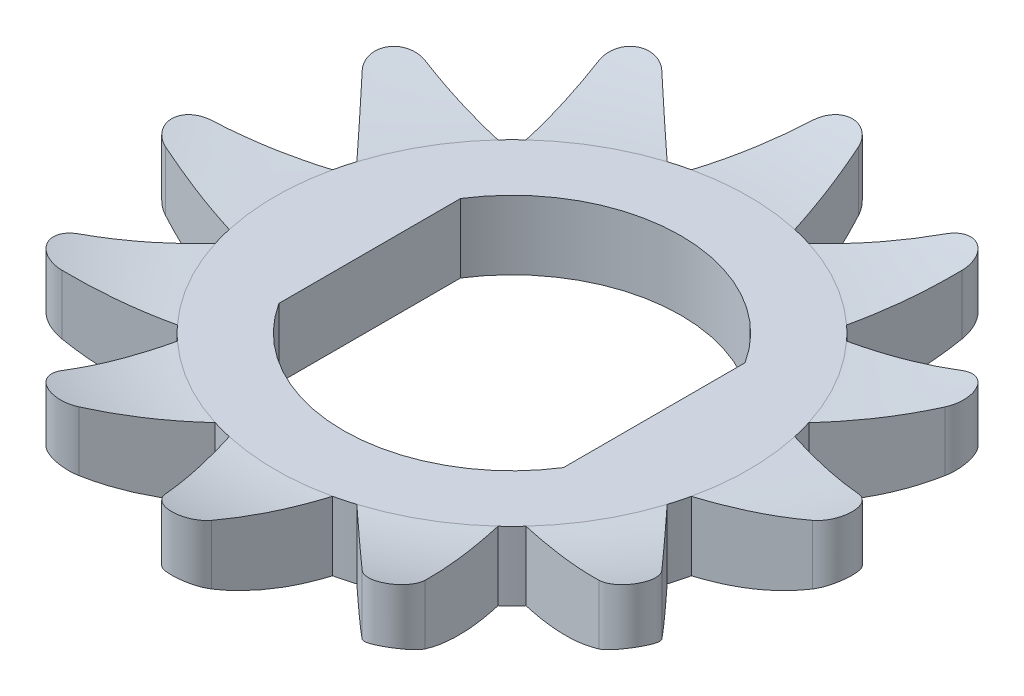
SolidWorks part; units mm, degrees
material "1060 Alloy"
ref_plane "Front Plane" through (0, 0, 0) normal (0, 0, 1) x (1, 0, 0)
ref_plane "Top Plane" through (0, 0, 0) normal (0, 1, 0) x (1, 0, 0)
ref_plane "Right Plane" through (0, 0, 0) normal (1, 0, 0) x (0, 0, -1)
sketch "Sketch1" plane through (0, 0, 0) normal (0, 1, 0) x (1, 0, 0)
  line L0 (0, 6.875) -> (0, 9.88) construction
  line L1 (-1.5, 6.7094) -> (-0.6685, 9.3876)
  line L2 (0.6685, 9.3876) -> (1.5, 6.7094)
  line L3 (2.0556, 6.5605) -> (4.1148, 8.4641)
  line L4 (5.2727, 7.7956) -> (4.6537, 5.0605)
  line L5 (5.0605, 4.6537) -> (7.7956, 5.2727)
  line L6 (8.4641, 4.1148) -> (6.5605, 2.0556)
  line L7 (6.7094, 1.5) -> (9.3876, 0.6685)
  line L8 (9.3876, -0.6685) -> (6.7094, -1.5)
  line L9 (6.5605, -2.0556) -> (8.4641, -4.1148)
  line L10 (7.7956, -5.2727) -> (5.0605, -4.6537)
  line L11 (4.6537, -5.0605) -> (5.2727, -7.7956)
  line L12 (4.1148, -8.4641) -> (2.0556, -6.5605)
  line L13 (1.5, -6.7094) -> (0.6685, -9.3876)
  line L14 (-0.6685, -9.3876) -> (-1.5, -6.7094)
  line L15 (-2.0556, -6.5605) -> (-4.1148, -8.4641)
  line L16 (-5.2727, -7.7956) -> (-4.6537, -5.0605)
  line L17 (-5.0605, -4.6537) -> (-7.7956, -5.2727)
  line L18 (-8.4641, -4.1148) -> (-6.5605, -2.0556)
  line L19 (-6.7094, -1.5) -> (-9.3876, -0.6685)
  line L20 (-9.3876, 0.6685) -> (-6.7094, 1.5)
  line L21 (-6.5605, 2.0556) -> (-8.4641, 4.1148)
  line L22 (-7.7956, 5.2727) -> (-5.0605, 4.6537)
  line L23 (-4.6537, 5.0605) -> (-5.2727, 7.7956)
  line L24 (-4.1148, 8.4641) -> (-2.0556, 6.5605)
  arc A1 (-4.6537, 5.0605) -> (-5.0605, 4.6537) centre (0, 0) ccw
  arc A2 (-0.6685, 9.3876) -> (0.6685, 9.3876) centre (0, 9.18) cw
  arc A3 (4.1148, 8.4641) -> (5.2727, 7.7956) centre (4.59, 7.9501) cw
  arc A4 (7.7956, 5.2727) -> (8.4641, 4.1148) centre (7.9501, 4.59) cw
  arc A5 (9.3876, 0.6685) -> (9.3876, -0.6685) centre (9.18, 0) cw
  arc A6 (8.4641, -4.1148) -> (7.7956, -5.2727) centre (7.9501, -4.59) cw
  arc A7 (5.2727, -7.7956) -> (4.1148, -8.4641) centre (4.59, -7.9501) cw
  arc A8 (0.6685, -9.3876) -> (-0.6685, -9.3876) centre (0, -9.18) cw
  arc A9 (-4.1148, -8.4641) -> (-5.2727, -7.7956) centre (-4.59, -7.9501) cw
  arc A10 (-7.7956, -5.2727) -> (-8.4641, -4.1148) centre (-7.9501, -4.59) cw
  arc A11 (-9.3876, -0.6685) -> (-9.3876, 0.6685) centre (-9.18, 0) cw
  arc A12 (-8.4641, 4.1148) -> (-7.7956, 5.2727) centre (-7.9501, 4.59) cw
  arc A13 (-5.2727, 7.7956) -> (-4.1148, 8.4641) centre (-4.59, 7.9501) cw
  arc A14 (-6.5605, 2.0556) -> (-6.7094, 1.5) centre (0, 0) ccw
  arc A15 (-6.7094, -1.5) -> (-6.5605, -2.0556) centre (0, 0) ccw
  arc A16 (-5.0605, -4.6537) -> (-4.6537, -5.0605) centre (0, 0) ccw
  arc A17 (-2.0556, -6.5605) -> (-1.5, -6.7094) centre (0, 0) ccw
  arc A18 (1.5, -6.7094) -> (2.0556, -6.5605) centre (0, 0) ccw
  arc A19 (4.6537, -5.0605) -> (5.0605, -4.6537) centre (0, 0) ccw
  arc A20 (6.5605, -2.0556) -> (6.7094, -1.5) centre (0, 0) ccw
  arc A21 (6.7094, 1.5) -> (6.5605, 2.0556) centre (0, 0) ccw
  arc A22 (5.0605, 4.6537) -> (4.6537, 5.0605) centre (0, 0) ccw
  arc A23 (2.0556, 6.5605) -> (1.5, 6.7094) centre (0, 0) ccw
  arc A24 (-1.5, 6.7094) -> (-2.0556, 6.5605) centre (0, 0) ccw
  point P10 (0, 9.88)
  point P69 (0, 0)
  dimension "D1" = 3.005
  dimension "D2" = 13.75
  dimension "D3" = 0.7
  dimension "D4" = 3
  dimension "D5" = 12
extrude "Boss-Extrude1" add sketch "Sketch1" along normal blind 2.45
sketch "Sketch2" plane through (0, 0, 0) normal (1, 0, 0) x (0, 0, -1)
  line L0 (6.875, 0) -> (-6.875, 0)
  line L1 (-7.7956, 0) -> (-5.0605, 0) construction
  line L2 (-1.5, 0) -> (-0.6685, 0) construction
  line L3 (-9.88, 2.45) -> (-9.88, 0.85)
  line L4 (-9.88, 2.45) -> (-9.88, 0) construction
  line L5 (0, 0) -> (0, 2) construction
  line L6 (0, 2) -> (-6.875, 2)
  line L7 (-6.875, 0) -> (-9.88, 0)
  line L8 (-9.88, 0) -> (-9.88, 0.85)
  line L9 (-9.88, 2.45) -> (0, 2.45)
  line L10 (0.6685, 2.45) -> (-0.6685, 2.45) construction
  line L11 (0, 2.45) -> (0, 2)
  arc A0 (-6.875, 0) -> (-9.88, 0.85) centre (-6.875, 5.7368) cw
  arc A1 (-6.875, 2) -> (-9.88, 2.45) centre (-6.875, 12.2584) cw
  dimension "D4" = 10.2584
  dimension "D5" = 5.7368
  dimension "D1" = 13.75
  dimension "D2" = 1.6
  dimension "D3" = 2
revolve "Cut-Revolve1" cut sketch "Sketch2" angle 360 about L5 region at (0, 0.2514, 9.1403)
sketch "Sketch3" plane through (0, 2, 0) normal (0, 1, 0) x (1, 0, 0)
  line L1 (-4.13, -2.6369) -> (-4.13, 2.6369)
  line L2 (4.13, -2.6369) -> (4.13, 2.6369)
  arc A0 (4.13, 2.6369) -> (-4.13, 2.6369) centre (0, 0) ccw
  arc A1 (-4.13, -2.6369) -> (4.13, -2.6369) centre (0, 0) ccw
  point P6 (0, 0)
  dimension "D1" = 9.8
  dimension "D2" = 8.26
extrude "Cut-Extrude1" cut sketch "Sketch3" against normal blind 2.45
